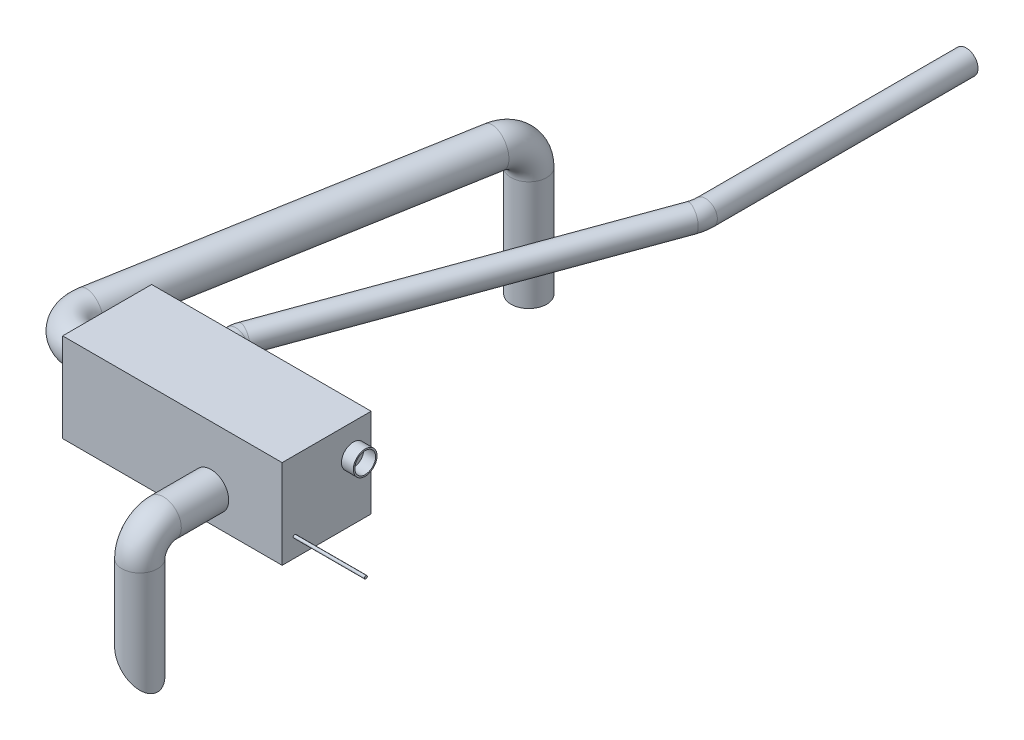
SolidWorks part; units mm, degrees
ref_plane "Front" through (0, 0, 0) normal (0, 0, 1) x (1, 0, 0)
ref_plane "Top" through (0, 0, 0) normal (0, 1, 0) x (1, 0, 0)
ref_plane "Right" through (0, 0, 0) normal (1, 0, 0) x (0, 0, -1)
sketch "Sketch1" plane through (0, 0, 0) normal (0, 1, 0) x (1, 0, 0)
  line L1 (-469.9, 190.5) -> (469.9, 190.5)
  line L2 (-469.9, 190.5) -> (-469.9, -190.5)
  line L3 (-469.9, -190.5) -> (469.9, -190.5)
  line L4 (469.9, 190.5) -> (469.9, -190.5)
  line L5 (-469.9, 190.5) -> (469.9, -190.5) construction
  line L6 (-469.9, -190.5) -> (469.9, 190.5) construction
  point P0 (0, 0)
  dimension "D1" = 381
  dimension "D2" = 939.8
extrude "Boss-Extrude1" add sketch "Sketch1" along normal blind 381
sketch "Sketch2" plane through (0, 0, 190.5) normal (0, 0, 1) x (1, 0, 0)
  line L0 (469.9, 381) -> (469.9, 0) construction
  line L1 (-469.9, 381) -> (469.9, 381) construction
  circle A0 centre (165.1, 127) radius 76.2
  circle A1 centre (165.1, 127) radius 69.85
  dimension "D1" = 152.4
  dimension "D3" = 254
  dimension "D4" = 139.7
  dimension "D2" = 304.8
extrude "Boss-Extrude2" add sketch "Sketch2" along normal blind 177.8
sketch "Sketch3" plane through (469.9, 0, 0) normal (1, 0, 0) x (0, 0, -1)
  line L0 (-190.5, 381) -> (190.5, 381) construction
  line L1 (190.5, 381) -> (190.5, 0) construction
  circle A0 centre (114.3, 254) radius 50.8
  circle A1 centre (114.3, 254) radius 44.45
  dimension "D1" = 101.6
  dimension "D2" = 88.9
  dimension "D3" = 127
  dimension "D4" = 76.2
extrude "Boss-Extrude3" add sketch "Sketch3" along normal blind 50.8
sketch "Sketch4" plane through (469.9, 0, 0) normal (1, 0, 0) x (0, 0, -1)
  circle A0 centre (-136.8501, 81.3511) radius 6.35
  dimension "D1" = 12.7
extrude "Boss-Extrude4" add sketch "Sketch4" along normal blind 304.8
sketch "Sketch5" plane through (0, 0, -190.5) normal (0, 0, -1) x (-1, 0, 0)
  line L0 (-469.9, 381) -> (469.9, 381) construction
  line L1 (469.9, 381) -> (469.9, 0) construction
  circle A0 centre (185.6926, 273.8882) radius 50.8
  circle A1 centre (185.6926, 273.8882) radius 44.45
  dimension "D1" = 101.6
  dimension "D2" = 88.9
  dimension "D4" = 284.2074
  dimension "D3" = 107.1118
extrude "Boss-Extrude5" add sketch "Sketch5" along normal blind 50.8
sketch "Sketch6" plane through (-469.9, 0, 0) normal (-1, 0, 0) x (0, 0, 1)
  line L0 (-190.5, 381) -> (190.5, 0) construction
  circle A0 centre (0, 190.5) radius 76.2
  circle A1 centre (0, 190.5) radius 69.85
  dimension "D1" = 152.4
  dimension "D2" = 139.7
extrude "Boss-Extrude6" add sketch "Sketch6" along normal blind 50.8
sketch "Sketch7" plane through (0, 0, 368.3) normal (0, 0, 1) x (1, 0, 0)
  circle A0 centre (165.1, 127) radius 76.2 construction
  circle A1 centre (165.1, 127) radius 76.2
  circle A2 centre (165.1, 127) radius 69.85 construction
  circle A3 centre (165.1, 127) radius 69.85
ref_point "Point1"
ref_plane "Plane1" through (165.1, 0, 0) normal (1, 0, 0) x (0, 0, -1)
sketch "Sketch8" plane through (165.1, 0, 0) normal (1, 0, 0) x (0, 0, -1)
  line L0 (-368.3, 127) -> (-393.7, 127)
  line L1 (-368.3, 203.2) -> (-368.3, 50.8) construction
  line L2 (-495.3, 25.4) -> (-495.3, -431.8)
  arc A0 (-393.7, 127) -> (-495.3, 25.4) centre (-393.7, 25.4) ccw
  dimension "D3" = 101.6
  dimension "D1" = 457.2
  dimension "D2" = 25.4
sweep "Sweep1" add profiles "Sketch7" path "Sketch8"
ref_point "Point2"
ref_plane "Plane2" through (0, 190.5, 0) normal (0, 1, 0) x (1, 0, 0)
sketch "Sketch9" plane through (0, 190.5, 0) normal (0, 1, 0) x (1, 0, 0)
  line L0 (-520.7, 0) -> (-546.1, 0)
  line L1 (-520.7, 76.2) -> (-520.7, -76.2) construction
  line L2 (-638.9947, 213.6) -> (677.326, 1625.6)
  line L3 (0, 0) -> (0, 1625.6) construction
  line L4 (0, 1625.6) -> (677.326, 1625.6) construction
  arc A0 (-546.1, 0) -> (-638.9947, 213.6) centre (-546.1, 127) cw
  dimension "D2" = 127
  dimension "D1" = 25.4
  dimension "D3" = 1930.4
  dimension "D4" = 1625.6
sketch "Sketch10" plane through (-520.7, 0, 0) normal (-1, 0, 0) x (0, 0, 1)
  circle A0 centre (0, 190.5) radius 76.2 construction
  circle A1 centre (0, 190.5) radius 76.2
  circle A2 centre (0, 190.5) radius 69.85 construction
  circle A3 centre (0, 190.5) radius 69.85
sweep "Sweep2" [suppressed] add profiles "Sketch10" path "Sketch9"
ref_point "Point3" [suppressed]
ref_point "Point4" [suppressed]
ref_plane "Plane3" [suppressed] through (1125.7423, 0, -1207.569) normal (0.6819, 0, -0.7315) x (-0.7315, 0, -0.6819)
ref_plane "Plane4" [suppressed] through (-448.4163, 0, -418.031) normal (0.7315, 0, 0.6819) x (0.6819, 0, -0.7315)
sketch "Sketch12" [suppressed] plane through (118.6492, 0, -1026.3147) normal (0.7315, 0, 0.6819) x (0.6819, 0, -0.7315)
  line L0 (844.7062, 190.5) -> (793.9062, 190.5) construction
  line L1 (641.5062, 38.1) -> (641.5062, -431.8) construction
  line L2 (-1157.5177, -431.8) -> (-1005.1177, -431.8) construction
  line L3 (819.3062, 190.5) -> (819.3062, 114.3) construction
  line L4 (997.1062, 38.1) -> (997.1062, -431.8)
  line L5 (844.7062, 190.5) -> (819.3062, 190.5)
  arc A0 (793.9062, 190.5) -> (641.5062, 38.1) centre (793.9062, 38.1) ccw construction
  arc A1 (844.7062, 190.5) -> (997.1062, 38.1) centre (844.7062, 38.1) cw
  dimension "D2" = 152.4
  dimension "D1" = 25.4
sketch "Sketch11" [suppressed] plane through (1125.7423, 0, -1207.569) normal (0.6819, 0, -0.7315) x (-0.7315, 0, -0.6819)
  circle A0 centre (613.0474, 190.5) radius 69.85 construction
  circle A1 centre (613.0474, 190.5) radius 76.2
  circle A2 centre (613.0474, 190.5) radius 76.2
  circle A3 centre (613.0474, 190.5) radius 69.85
  dimension "D1" = 0
sweep "Sweep4" [suppressed] add profiles "Sketch11" path "Sketch12"
ref_point "Point5"
ref_plane "Plane5" through (0, 273.8882, 0) normal (0, 1, 0) x (1, 0, 0)
sketch "Sketch13" plane through (0, 273.8882, 0) normal (0, 1, 0) x (1, 0, 0)
  line L0 (-185.6926, 241.3) -> (-185.6926, 266.7)
  line L1 (-134.8926, 241.3) -> (-236.4926, 241.3) construction
  line L2 (-181.0972, 292.7619) -> (330.9506, 1699.6019)
  line L3 (340.1415, 1751.7257) -> (340.1415, 2867.8535)
  line L4 (469.9, 190.5) -> (-469.9, 190.5) construction
  arc A0 (-185.6926, 266.7) -> (-181.0972, 292.7619) centre (-109.4926, 266.7) cw
  arc A1 (340.1415, 1751.7257) -> (330.9506, 1699.6019) centre (187.7415, 1751.7257) cw
  point P6 (417.4268, 1698.7399)
  point P13 (340.1415, 1724.8535)
  dimension "D1" = 76.2
  dimension "D6" = 152.4
  dimension "D2" = 25.4
  dimension "D3" = 1524
  dimension "D4" = 1143
  dimension "D5" = 70
sketch "Sketch14" plane through (0, 0, -241.3) normal (0, 0, -1) x (-1, 0, 0)
  circle A0 centre (185.6926, 273.8882) radius 44.45 construction
  circle A1 centre (185.6926, 273.8882) radius 50.8
  circle A2 centre (185.6926, 273.8882) radius 50.8
  circle A3 centre (185.6926, 273.8882) radius 44.45
  dimension "D1" = 0
sweep "Sweep5" add profiles "Sketch14" path "Sketch13"
sketch "Sketch15" [suppressed] plane through (0, 273.8882, 0) normal (0, 1, 0) x (1, 0, 0)
  line L0 (-185.6926, 241.3) -> (-185.6926, 317.5)
  line L1 (-134.8926, 241.3) -> (-236.4926, 241.3) construction
  line L2 (-177.0378, 383.24) -> (204.2544, 1806.242)
  line L3 (469.9, 190.5) -> (-469.9, 190.5) construction
  line L4 (221.5641, 1937.722) -> (221.5641, 2852.122)
  arc A0 (-185.6926, 317.5) -> (-177.0378, 383.24) centre (68.3074, 317.5) cw
  arc A1 (204.2544, 1806.242) -> (221.5641, 1937.722) centre (-286.4359, 1937.722) ccw
  dimension "D2" = 254
  dimension "D4" = 508
  dimension "D1" = 76.2
  dimension "D3" = 45
  dimension "D5" = 1016
  dimension "D6" = 1524
sketch "Sketch16" [suppressed] plane through (0, 0, -241.3) normal (0, 0, -1) x (-1, 0, 0)
  circle A0 centre (185.6926, 273.8882) radius 44.45 construction
  circle A1 centre (185.6926, 273.8882) radius 50.8
  circle A2 centre (185.6926, 273.8882) radius 50.8
  circle A3 centre (185.6926, 273.8882) radius 44.45
  dimension "D1" = 0
sweep "Sweep6" [suppressed] add profiles "Sketch16" path "Sketch15"
sketch "Sketch17" [suppressed] plane through (0, 0, 190.5) normal (0, 0, 1) x (1, 0, 0)
  line L0 (241.3, -203.2) -> (12.7, -431.8)
  line L1 (12.7, -431.8) -> (241.3, -431.8)
  line L2 (241.3, -431.8) -> (241.3, -203.2)
  line L3 (722.3661, -431.8) -> (874.7661, -431.8) construction
  line L4 (88.9, -431.8) -> (241.3, -431.8) construction
  line L5 (241.3, -431.8) -> (241.3, 25.4) construction
  dimension "D1" = 45
  dimension "D2" = 228.6
extrude "Cut-Extrude1" [suppressed] cut sketch "Sketch17" along normal blind 457.962
sketch "Sketch18" plane through (0, 190.5, 0) normal (0, 1, 0) x (1, 0, 0)
  line L0 (-520.7, 0) -> (-571.5, 0)
  line L1 (-520.7, 76.2) -> (-520.7, -76.2) construction
  line L2 (-696.5706, 149.0533) -> (-440.7521, 1599.8721)
  arc A0 (-571.5, 0) -> (-696.5706, 149.0533) centre (-571.5, 127) cw
  point P7 (-242.3702, 1788.4183)
  dimension "D1" = 127
  dimension "D2" = 1473.2
  dimension "D3" = 80
  dimension "D4" = 50.8
sketch "Sketch19" plane through (-520.7, 0, 0) normal (-1, 0, 0) x (0, 0, 1)
  circle A0 centre (0, 190.5) radius 69.85 construction
  circle A1 centre (0, 190.5) radius 76.2
  circle A2 centre (0, 190.5) radius 76.2
  circle A3 centre (0, 190.5) radius 69.85
  dimension "D1" = 0
sweep "Sweep7" add profiles "Sketch19" path "Sketch18"
ref_axis "Axis1" through (-688.8567, 190.5, -192.8009) along (0.1736, 0, -0.9848)
ref_point "Point6"
ref_point "Point7"
ref_plane "Plane6" through (-701.056, 0, -123.6151) normal (-0.9848, 0, -0.1736) x (-0.1736, 0, 0.9848)
sketch "Sketch20" plane through (-701.056, 0, -123.6151) normal (-0.9848, 0, -0.1736) x (-0.1736, 0, 0.9848)
  line L0 (-1499.0307, 190.5) -> (-1524.4307, 190.5)
  line L1 (-1651.4307, 63.5) -> (-1651.4307, -406.4)
  arc A0 (-1524.4307, 190.5) -> (-1651.4307, 63.5) centre (-1524.4307, 63.5) ccw
  point P5 (-1759.1341, 53.1154)
  dimension "D2" = 127
  dimension "D1" = 25.4
  dimension "D3" = 469.9
sketch "Sketch21" plane through (260.3039, 0, -1476.257) normal (0.1736, 0, -0.9848) x (-0.9848, 0, -0.1736)
  circle A0 centre (711.8709, 190.5) radius 69.85 construction
  circle A1 centre (711.8709, 190.5) radius 76.2
  circle A2 centre (711.8709, 190.5) radius 76.2
  circle A3 centre (711.8709, 190.5) radius 69.85
  dimension "D1" = 0
sweep "Sweep8" add profiles "Sketch21" path "Sketch20"
sketch "Sketch22" plane through (0, 0, 190.5) normal (0, 0, 1) x (1, 0, 0)
  line L0 (88.9, -279.4) -> (241.3, -431.8)
  line L1 (88.9, 25.4) -> (88.9, -431.8) construction
  line L2 (241.3, -431.8) -> (88.9, -431.8)
  line L3 (88.9, -431.8) -> (88.9, -279.4)
  dimension "D1" = 45
extrude "Cut-Extrude3" cut sketch "Sketch22" along normal through all
